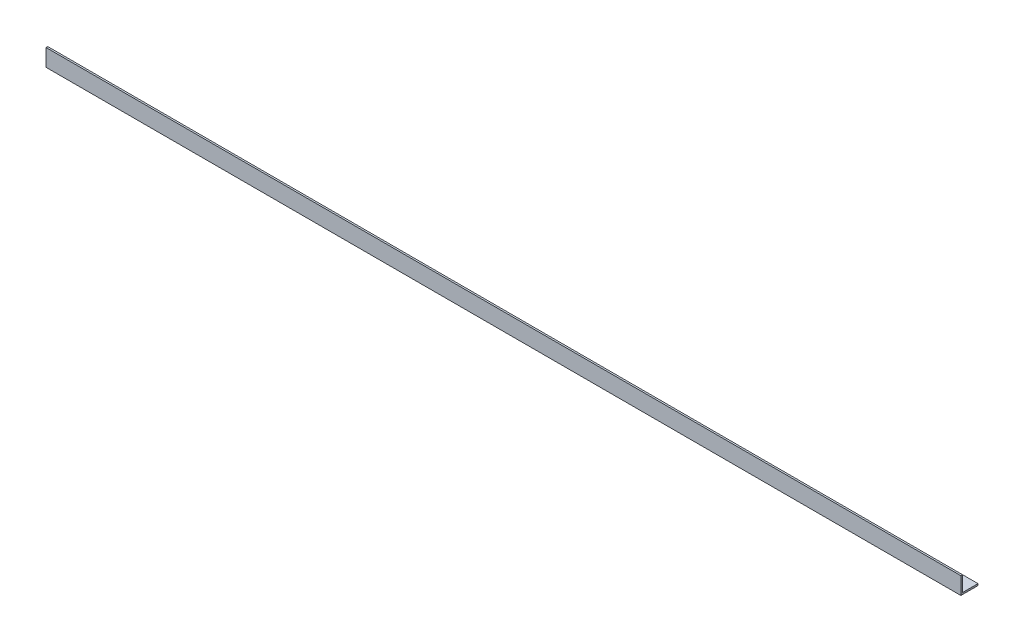
SolidWorks part; units mm, degrees
ref_plane "Спереди" through (0, 0, 0) normal (0, 0, 1) x (1, 0, 0)
ref_plane "Сверху" through (0, 0, 0) normal (0, 1, 0) x (1, 0, 0)
ref_plane "Справа" through (0, 0, 0) normal (1, 0, 0) x (0, 0, -1)
sketch "Эскиз1" plane through (0, 0, 0) normal (1, 0, 0) x (0, 0, -1)
  line L0 (0, 50) -> (0, 0)
  line L1 (0, 0) -> (50, 0)
extrude "Вытянуть-Тонкостенный1" add sketch "Эскиз1" along normal blind 2665 thin thin type one direction reverse wall 5
